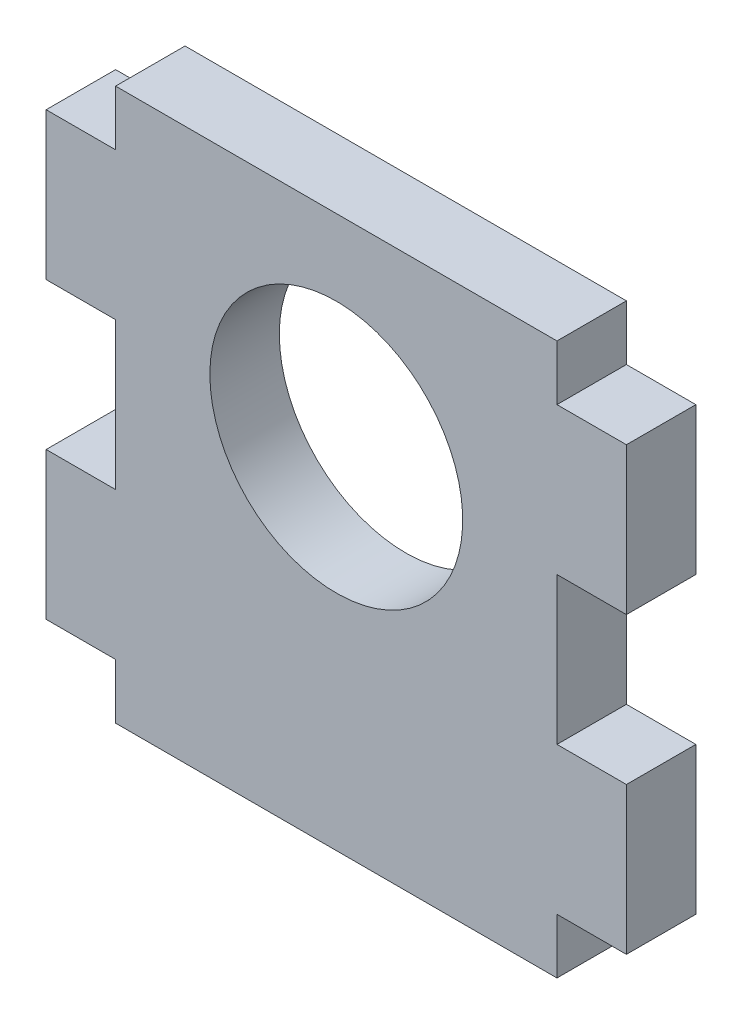
SolidWorks part; units mm, degrees
ref_plane "Front Plane" through (0, 0, 0) normal (0, 0, 1) x (1, 0, 0)
ref_plane "Top Plane" through (0, 0, 0) normal (0, 1, 0) x (1, 0, 0)
ref_plane "Right Plane" through (0, 0, 0) normal (1, 0, 0) x (0, 0, -1)
sketch "Sketch1" plane through (0, 0, 0) normal (0, 0, 1) x (1, 0, 0)
  line L0 (0, 19.05) -> (0, -31.75) construction
  line L1 (19.05, 19.05) -> (-19.05, 19.05)
  line L2 (19.05, 19.05) -> (19.05, 12.7)
  line L3 (19.05, -31.75) -> (-19.05, -31.75)
  line L4 (-19.05, 19.05) -> (-19.05, 12.7)
  line L5 (-19.05, -6.35) -> (19.05, -6.35) construction
  line L6 (-25.0444, -25.4) -> (-25.0444, -12.7)
  line L7 (-19.05, 12.7) -> (-25.0444, 12.7)
  line L8 (-19.05, -25.4) -> (-19.05, -31.75)
  line L9 (-19.05, 0) -> (-25.0444, 0)
  line L10 (-25.0444, 12.7) -> (-25.0444, 0)
  line L11 (-19.05, -12.7) -> (-25.0444, -12.7)
  line L12 (19.05, -25.4) -> (19.05, -31.75)
  line L13 (-19.05, -25.4) -> (-25.0444, -25.4)
  line L14 (19.05, -25.4) -> (25.0444, -25.4)
  line L15 (19.05, 0) -> (19.05, -12.7)
  line L16 (19.05, -12.7) -> (25.0444, -12.7)
  line L17 (25.0444, 12.7) -> (25.0444, 0)
  line L18 (19.05, 0) -> (25.0444, 0)
  line L20 (19.05, 12.7) -> (25.0444, 12.7)
  line L21 (25.0444, -25.4) -> (25.0444, -12.7)
  line L22 (-19.05, 0) -> (-19.05, -12.7)
  circle A0 centre (0, 0) radius 10.9125
  dimension "D1" = 21.825
  dimension "D2" = 19.05
  dimension "D3" = 38.1
  dimension "D4" = 50.8
  dimension "D5" = 5.9944
  dimension "D6" = 12.7
  dimension "D7" = 6.35
extrude "Boss-Extrude1" add sketch "Sketch1" along normal blind 5.9944
sketch "Sketch2" plane through (0, 0, 5.9944) normal (0, 0, 1) x (1, 0, 0)
  line L0 (19.05, -31.75) -> (19.05, -25.4) construction
  line L1 (-19.05, -31.75) -> (19.05, -31.75)
  line L2 (-19.05, -31.75) -> (-19.05, -30.1625)
  line L3 (-19.05, -30.1625) -> (19.05, -30.1625)
  line L4 (19.05, -31.75) -> (19.05, -30.1625)
  line L5 (19.05, 12.7) -> (19.05, 19.05) construction
  line L6 (-19.05, 19.05) -> (19.05, 19.05)
  line L7 (-19.05, 19.05) -> (-19.05, 17.4625)
  line L8 (-19.05, 17.4625) -> (19.05, 17.4625)
  line L9 (19.05, 19.05) -> (19.05, 17.4625)
  dimension "D1" = 1.5875
  dimension "D2" = 1.5875
extrude "Cut-Extrude1" cut sketch "Sketch2" against normal through all
